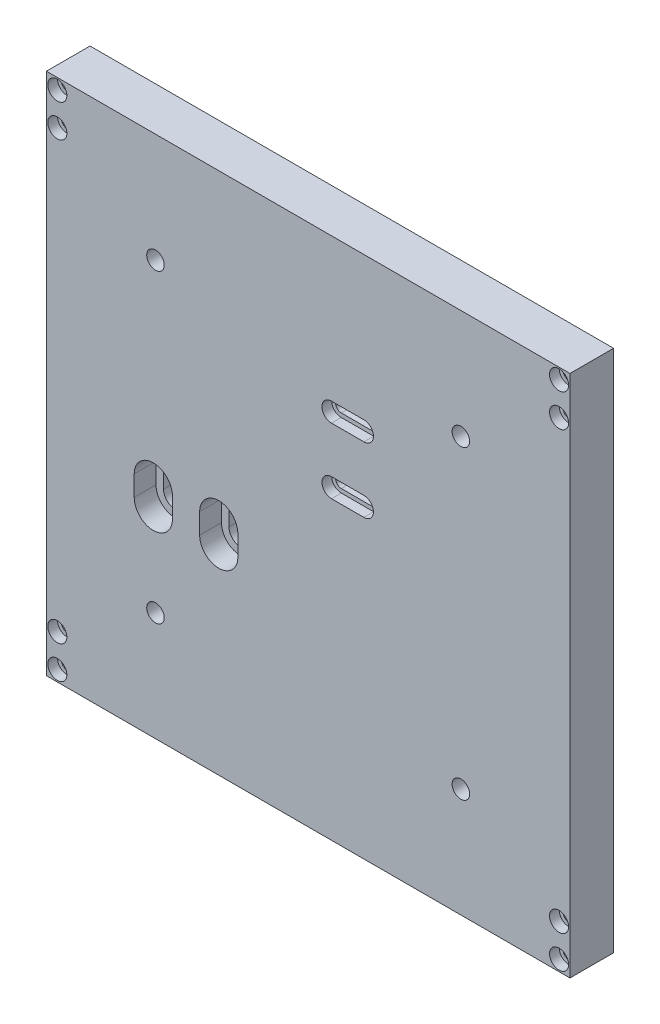
SolidWorks part; units mm, degrees
ref_plane "Front Plane" through (0, 0, 0) normal (0, 0, 1) x (1, 0, 0)
ref_plane "Top Plane" through (0, 0, 0) normal (0, 1, 0) x (1, 0, 0)
ref_plane "Right Plane" through (0, 0, 0) normal (1, 0, 0) x (0, 0, -1)
sketch "Sketch1" plane through (0, 0, 0) normal (0, 0, 1) x (1, 0, 0)
  line L1 (-76.2, -76.2) -> (76.2, -76.2)
  line L2 (-76.2, -76.2) -> (-76.2, 76.2)
  line L3 (-76.2, 76.2) -> (76.2, 76.2)
  line L4 (76.2, -76.2) -> (76.2, 76.2)
  line L5 (-76.2, -76.2) -> (76.2, 76.2) construction
  line L6 (-76.2, 76.2) -> (76.2, -76.2) construction
  point P0 (0, 0)
  dimension "D1" = 152.4
  dimension "D2" = 152.4
extrude "Boss-Extrude1" add sketch "Sketch1" along normal blind 12.7 contours L3 L4 L1 L2
ref_plane "Plane1" through (0, 0, 0) normal (-1, 0, 0) x (0, 0, 1)
ref_plane "Plane2" through (0, 0, 0) normal (0, 1, 0) x (1, 0, 0)
hole_wizard "1/4-20 Tapped Hole1" positions "Sketch8" profile "Sketch9" tap size "1/4-20" standard "ANSI Inch" end condition through all
sketch "Sketch8" plane through (0, 0, 12.7) normal (0, 0, 1) x (1, 0, 0)
  line L0 (0, 3.4925) -> (0, -3.4925) construction
  line L1 (3.4925, 0) -> (-3.4925, 0) construction
  point P0 (44.45, 44.45)
  point P7 (44.45, -44.45)
  point P8 (-44.45, -44.45)
  point P9 (-44.45, 44.45)
  dimension "D1" = 44.45
  dimension "D2" = 44.45
sketch "Sketch9" plane through (44.45, 44.45, 12.7) normal (1, 0, 0) x (0, -1, 0)
  line L0 (0, 0) -> (0, 12.7)
  line L1 (0, 12.7) -> (2.5527, 12.7)
  line L2 (2.5527, 12.7) -> (2.5527, 0)
  line L5 (2.5527, 0) -> (0, 0)
  line L11 (0, -6.35) -> (0, 107.95) construction
  dimension "Thread Major Dia." = 5.1054
  dimension "Thru Tap Drill Depth" = 12.7
hole_wizard "CBORE for #4 Socket Head Cap Screw1" positions "Sketch10" profile "Sketch12" counterbore size "#4" standard "ANSI Inch" end condition through all
sketch "Sketch10" plane through (0, 0, 12.7) normal (0, 0, 1) x (1, 0, 0)
  line L0 (-76.2, -76.2) -> (-76.2, 76.2) construction
  line L1 (-76.2, 76.2) -> (76.2, 76.2) construction
  line L2 (0, 3.4925) -> (0, -3.4925) construction
  line L3 (3.4925, 0) -> (-3.4925, 0) construction
  point P0 (-73.025, 63.5)
  point P2 (-73.025, 73.025)
  point P11 (73.025, 63.5)
  point P12 (73.025, 73.025)
  point P16 (73.025, -63.5)
  point P17 (73.025, -73.025)
  point P18 (-73.025, -63.5)
  point P19 (-73.025, -73.025)
  dimension "D1" = 3.175
  dimension "D2" = 3.175
  dimension "D3" = 3.175
  dimension "D4" = 12.7
sketch "Sketch12" plane through (-73.025, 63.5, 12.7) normal (1, 0, 0) x (0, -1, 0)
  line L0 (0, 0) -> (0, 12.7)
  line L1 (0, 12.7) -> (1.6319, 12.7)
  line L3 (1.6319, 12.7) -> (1.6319, 2.8448)
  line L4 (1.6319, 2.8448) -> (2.7788, 2.8448)
  line L5 (2.7788, 2.8448) -> (2.7788, 0)
  line L7 (2.7788, 0) -> (0, 0)
  line L11 (0, -6.35) -> (0, 107.95) construction
  dimension "Thru Hole Dia." = 3.2639
  dimension "Thru Hole Depth" = 12.7
  dimension "C'Bore Dia." = 5.5575
  dimension "C'Bore Depth" = 2.8448
hole_wizard "#2-56 Tapped Hole1" positions "Sketch13" profile "Sketch14" tap size "#2-56" standard "ANSI Inch"
sketch "Sketch13" plane through (0, 0, 0) normal (0, 0, -1) x (-1, 0, 0)
  line L0 (-76.2, -76.2) -> (-76.2, 76.2) construction
  line L1 (76.2, -76.2) -> (-76.2, -76.2) construction
  point P0 (-63.5, -63.5)
  point P2 (-63.5, -34.163)
  point P4 (-29.083, -63.5)
  point P6 (-29.083, -34.163)
  dimension "D1" = 12.7
  dimension "D2" = 12.7
  dimension "D3" = 12.7
  dimension "D4" = 29.337
  dimension "D5" = 12.7
  dimension "D6" = 34.417
  dimension "D7" = 29.337
  dimension "D8" = 34.417
sketch "Sketch14" plane through (63.5, -63.5, 0) normal (1, 0, 0) x (0, 1, 0)
  line L0 (0, 0) -> (0, 6.2746)
  line L1 (0, 6.2746) -> (0.889, 5.7404)
  line L2 (0.889, 5.7404) -> (0.889, 0)
  line L5 (0.889, 0) -> (0, 0)
  line L10 (0, 6.2746) -> (-0.889, 5.7404) construction
  line L11 (0, -6.35) -> (0, 107.95) construction
  dimension "Tap Drill Dia." = 1.778
  dimension "Tap Drill Depth" = 5.7404
  dimension "Drill Angle" = 118
cosmetic thread "Hole Thread1"
cosmetic thread "Hole Thread2"
cosmetic thread "Hole Thread3"
cosmetic thread "Hole Thread4"
hole_wizard "#2-56 Tapped Hole2" positions "Sketch15" profile "Sketch16" tap size "#2-56" standard "ANSI Inch"
sketch "Sketch15" plane through (0, 0, 0) normal (0, 0, -1) x (-1, 0, 0)
  line L0 (-76.2, -76.2) -> (-76.2, 76.2) construction
  line L1 (76.2, 76.2) -> (-76.2, 76.2) construction
  point P0 (-63.5, 6.5278)
  point P2 (-63.5, 63.5)
  point P4 (-29.3878, 63.5)
  point P6 (-29.3878, 6.5278)
  dimension "D1" = 12.7
  dimension "D2" = 12.7
  dimension "D3" = 12.7
  dimension "D4" = 12.7
  dimension "D5" = 56.9722
  dimension "D6" = 56.9722
  dimension "D7" = 34.1122
  dimension "D8" = 34.1122
sketch "Sketch16" plane through (63.5, 6.5278, 0) normal (1, 0, 0) x (0, 1, 0)
  line L0 (0, 0) -> (0, 6.2746)
  line L1 (0, 6.2746) -> (0.889, 5.7404)
  line L2 (0.889, 5.7404) -> (0.889, 0)
  line L5 (0.889, 0) -> (0, 0)
  line L10 (0, 6.2746) -> (-0.889, 5.7404) construction
  line L11 (0, -6.35) -> (0, 107.95) construction
  dimension "Tap Drill Dia." = 1.778
  dimension "Tap Drill Depth" = 5.7404
  dimension "Drill Angle" = 118
cosmetic thread "Hole Thread5"
cosmetic thread "Hole Thread6"
cosmetic thread "Hole Thread7"
cosmetic thread "Hole Thread8"
hole_wizard "CBORE SLOT for #4 Socket Head Cap Screw1" positions "Sketch17" profile "Sketch18" size "#4" standard "ANSI Inch" slot yes end condition through all
sketch "Sketch17" plane through (0, 0, 12.7) normal (0, 0, 1) x (1, 0, 0)
  line L0 (5.1562, 12.7) -> (17.8562, 12.7) construction
  line L1 (-76.2, -76.2) -> (-76.2, 76.2) construction
  line L2 (-76.2, 76.2) -> (76.2, 76.2) construction
  point P0 (11.5062, 12.7)
  point P2 (11.5062, 31.75)
  dimension "D1" = 87.7062
  dimension "D2" = 12.7
  dimension "D3" = 87.7062
  dimension "D4" = 44.45
  dimension "D5" = 19.05
sketch "Sketch18" plane through (11.5062, 12.7, 12.7) normal (1, 0, 0) x (0, -1, 0)
  line L0 (0, 0) -> (0, 12.7)
  line L1 (0, 12.7) -> (1.6319, 12.7)
  line L3 (1.6319, 12.7) -> (1.632, 2.8448)
  line L4 (1.632, 2.8448) -> (2.7788, 2.8448)
  line L5 (2.7788, 2.8448) -> (2.7788, 0)
  line L7 (2.7788, 0) -> (0, 0)
  line L11 (0, -6.35) -> (0, 107.95) construction
  dimension "Thru Hole Dia." = 3.2639
  dimension "Thru Hole Depth" = 12.7
  dimension "C'Bore Dia." = 5.5575
  dimension "C'Bore Depth" = 2.8448
hole_wizard "CBORE SLOT for 1/4 Socket Head Cap Screw3" positions "Sketch21" profile "Sketch22" size "1/4" standard "ANSI Inch" slot yes
sketch "Sketch21" plane through (0, 0, 12.7) normal (0, 0, 1) x (1, 0, 0)
  line L0 (-26.035, -21.844) -> (-26.035, -9.144) construction
  line L1 (-76.2, 76.2) -> (76.2, 76.2) construction
  line L2 (-76.2, -76.2) -> (-76.2, 76.2) construction
  point P0 (-26.035, -15.494)
  point P4 (-45.085, -15.494)
  dimension "D1" = 12.7
  dimension "D2" = 19.05
  dimension "D3" = 91.694
  dimension "D4" = 91.694
  dimension "D5" = 31.115
sketch "Sketch22" plane through (-26.035, -15.494, 12.7) normal (1, 0, 0) x (0, -1, 0)
  line L0 (0, 0) -> (0, 18.5398)
  line L1 (0, 18.5398) -> (3.3782, 16.51)
  line L2 (3.3782, 16.51) -> (3.3782, 6.35)
  line L3 (3.3782, 6.35) -> (5.5562, 6.35)
  line L4 (5.5562, 6.35) -> (5.5562, 0)
  line L5 (5.5562, 0) -> (0, 0)
  line L10 (0, 18.5398) -> (-3.3782, 16.51) construction
  line L11 (0, -6.35) -> (0, 107.95) construction
  dimension "Hole Dia." = 6.7564
  dimension "Hole Depth" = 16.51
  dimension "C'Bore Dia." = 11.1125
  dimension "C'Bore Depth" = 6.35
  dimension "Drill Angle" = 118
